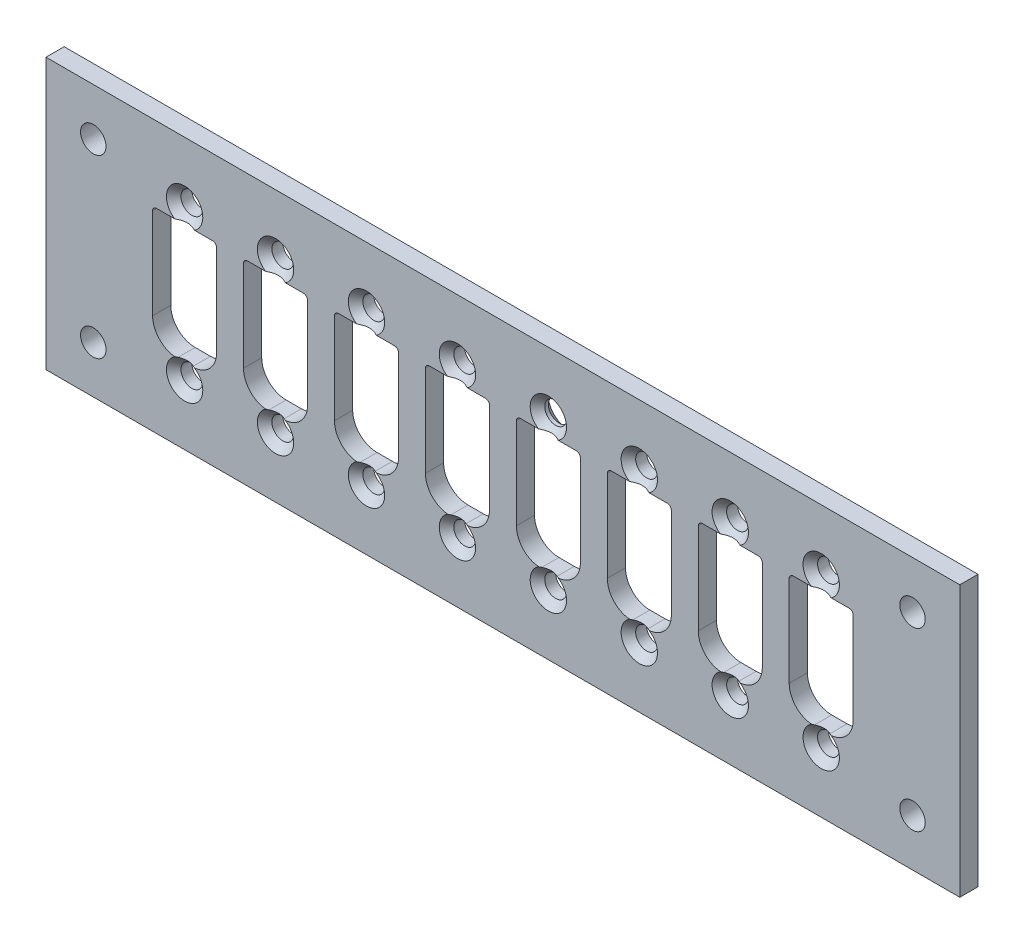
SolidWorks part; units mm, degrees
ref_plane "Front Plane" through (0, 0, 0) normal (0, 0, 1) x (1, 0, 0)
ref_plane "Top Plane" through (0, 0, 0) normal (0, 1, 0) x (1, 0, 0)
ref_plane "Right Plane" through (0, 0, 0) normal (1, 0, 0) x (0, 0, -1)
sketch "Sketch1" plane through (0, 0, 11.1151) normal (0, 0, -1) x (-1, 0, 0)
  line L0 (-135.406, 8.4004) -> (-129.506, 8.4004) construction
  line L1 (-151.506, 40.6004) -> (-25.906, 40.6004)
  line L2 (-151.506, 40.6004) -> (-151.506, 3.4004)
  line L3 (-151.506, 3.4004) -> (-25.906, 3.4004)
  line L4 (-25.906, 40.6004) -> (-25.906, 3.4004)
  line L5 (-129.506, 35.6004) -> (-135.406, 35.6004) construction
  line L6 (-40.906, 17.1504) -> (-40.906, 29.6504) construction
  line L7 (-41.106, 29.8504) -> (-48.806, 29.8504) construction
  line L8 (-49.006, 29.6504) -> (-49.006, 17.1504) construction
  line L9 (-46.006, 14.1504) -> (-43.906, 14.1504) construction
  line L10 (-53.406, 17.1504) -> (-53.406, 29.6504) construction
  line L11 (-53.606, 29.8504) -> (-61.306, 29.8504) construction
  line L12 (-61.506, 29.6504) -> (-61.506, 17.1504) construction
  line L13 (-58.506, 14.1504) -> (-56.406, 14.1504) construction
  line L14 (-65.906, 17.1504) -> (-65.906, 29.6504) construction
  line L15 (-66.106, 29.8504) -> (-73.806, 29.8504) construction
  line L16 (-74.006, 29.6504) -> (-74.006, 17.1504) construction
  line L17 (-71.006, 14.1504) -> (-68.906, 14.1504) construction
  line L18 (-78.406, 17.1504) -> (-78.406, 29.6504) construction
  line L19 (-78.606, 29.8504) -> (-86.306, 29.8504) construction
  line L20 (-86.506, 29.6504) -> (-86.506, 17.1504) construction
  line L21 (-83.506, 14.1504) -> (-81.406, 14.1504) construction
  line L22 (-90.906, 17.1504) -> (-90.906, 29.6504) construction
  line L23 (-91.106, 29.8504) -> (-98.806, 29.8504) construction
  line L24 (-99.006, 29.6504) -> (-99.006, 17.1504) construction
  line L25 (-96.006, 14.1504) -> (-93.906, 14.1504) construction
  line L26 (-103.406, 17.1504) -> (-103.406, 29.6504) construction
  line L27 (-103.606, 29.8504) -> (-111.306, 29.8504) construction
  line L28 (-111.506, 29.6504) -> (-111.506, 17.1504) construction
  line L29 (-108.506, 14.1504) -> (-106.406, 14.1504) construction
  line L30 (-115.906, 17.1504) -> (-115.906, 29.6504) construction
  line L31 (-116.106, 29.8504) -> (-123.806, 29.8504) construction
  line L32 (-124.006, 29.6504) -> (-124.006, 17.1504) construction
  line L33 (-121.006, 14.1504) -> (-118.906, 14.1504) construction
  line L34 (-128.406, 17.1504) -> (-128.406, 29.6504) construction
  line L35 (-128.606, 29.8504) -> (-136.306, 29.8504) construction
  line L36 (-136.506, 29.6504) -> (-136.506, 17.1504) construction
  line L37 (-133.506, 14.1504) -> (-131.406, 14.1504) construction
  line L38 (-40.906, 17.1504) -> (-40.906, 29.6504) construction
  line L39 (-41.106, 29.8504) -> (-48.806, 29.8504) construction
  line L40 (-49.006, 29.6504) -> (-49.006, 17.1504) construction
  line L41 (-46.006, 14.1504) -> (-43.906, 14.1504) construction
  line L42 (-53.406, 17.1504) -> (-53.406, 29.6504) construction
  line L43 (-53.606, 29.8504) -> (-61.306, 29.8504) construction
  line L44 (-61.506, 29.6504) -> (-61.506, 17.1504) construction
  line L45 (-58.506, 14.1504) -> (-56.406, 14.1504) construction
  line L46 (-65.906, 17.1504) -> (-65.906, 29.6504) construction
  line L47 (-66.106, 29.8504) -> (-73.806, 29.8504) construction
  line L48 (-74.006, 29.6504) -> (-74.006, 17.1504) construction
  line L49 (-71.006, 14.1504) -> (-68.906, 14.1504) construction
  line L50 (-78.406, 17.1504) -> (-78.406, 29.6504) construction
  line L51 (-78.606, 29.8504) -> (-86.306, 29.8504) construction
  line L52 (-86.506, 29.6504) -> (-86.506, 17.1504) construction
  line L53 (-83.506, 14.1504) -> (-81.406, 14.1504) construction
  line L54 (-90.906, 17.1504) -> (-90.906, 29.6504) construction
  line L55 (-91.106, 29.8504) -> (-98.806, 29.8504) construction
  line L56 (-99.006, 29.6504) -> (-99.006, 17.1504) construction
  line L57 (-96.006, 14.1504) -> (-93.906, 14.1504) construction
  line L58 (-103.406, 17.1504) -> (-103.406, 29.6504) construction
  line L59 (-103.606, 29.8504) -> (-111.306, 29.8504) construction
  line L60 (-111.506, 29.6504) -> (-111.506, 17.1504) construction
  line L61 (-108.506, 14.1504) -> (-106.406, 14.1504) construction
  line L62 (-115.906, 17.1504) -> (-115.906, 29.6504) construction
  line L63 (-116.106, 29.8504) -> (-123.806, 29.8504) construction
  line L64 (-124.006, 29.6504) -> (-124.006, 17.1504) construction
  line L65 (-121.006, 14.1504) -> (-118.906, 14.1504) construction
  line L66 (-128.406, 17.1504) -> (-128.406, 29.6504) construction
  line L67 (-128.606, 29.8504) -> (-136.306, 29.8504) construction
  line L68 (-136.506, 29.6504) -> (-136.506, 17.1504) construction
  line L69 (-133.506, 14.1504) -> (-131.406, 14.1504) construction
  line L70 (-61.856, 29.6504) -> (-61.856, 17.1504)
  line L71 (-58.506, 13.8004) -> (-56.406, 13.8004)
  line L72 (-53.056, 17.1504) -> (-53.056, 29.6504)
  line L73 (-53.606, 30.2004) -> (-61.306, 30.2004)
  line L74 (-49.356, 29.6504) -> (-49.356, 17.1504)
  line L75 (-46.006, 13.8004) -> (-43.906, 13.8004)
  line L76 (-40.556, 17.1504) -> (-40.556, 29.6504)
  line L77 (-41.106, 30.2004) -> (-48.806, 30.2004)
  line L78 (-74.356, 29.6504) -> (-74.356, 17.1504)
  line L79 (-71.006, 13.8004) -> (-68.906, 13.8004)
  line L80 (-65.556, 17.1504) -> (-65.556, 29.6504)
  line L81 (-66.106, 30.2004) -> (-73.806, 30.2004)
  line L82 (-86.856, 29.6504) -> (-86.856, 17.1504)
  line L83 (-83.506, 13.8004) -> (-81.406, 13.8004)
  line L84 (-78.056, 17.1504) -> (-78.056, 29.6504)
  line L85 (-78.606, 30.2004) -> (-86.306, 30.2004)
  line L86 (-99.356, 29.6504) -> (-99.356, 17.1504)
  line L87 (-96.006, 13.8004) -> (-93.906, 13.8004)
  line L88 (-90.556, 17.1504) -> (-90.556, 29.6504)
  line L89 (-91.106, 30.2004) -> (-98.806, 30.2004)
  line L90 (-111.856, 29.6504) -> (-111.856, 17.1504)
  line L91 (-108.506, 13.8004) -> (-106.406, 13.8004)
  line L92 (-103.056, 17.1504) -> (-103.056, 29.6504)
  line L93 (-103.606, 30.2004) -> (-111.306, 30.2004)
  line L94 (-124.356, 29.6504) -> (-124.356, 17.1504)
  line L95 (-121.006, 13.8004) -> (-118.906, 13.8004)
  line L96 (-115.556, 17.1504) -> (-115.556, 29.6504)
  line L97 (-116.106, 30.2004) -> (-123.806, 30.2004)
  line L98 (-136.856, 29.6504) -> (-136.856, 17.1504)
  line L99 (-133.506, 13.8004) -> (-131.406, 13.8004)
  line L100 (-128.056, 17.1504) -> (-128.056, 29.6504)
  line L101 (-128.606, 30.2004) -> (-136.306, 30.2004)
  arc A0 (-43.906, 14.1504) -> (-40.906, 17.1504) centre (-43.906, 17.1504) ccw construction
  arc A1 (-40.906, 29.6504) -> (-41.106, 29.8504) centre (-41.106, 29.6504) ccw construction
  arc A2 (-48.806, 29.8504) -> (-49.006, 29.6504) centre (-48.806, 29.6504) ccw construction
  arc A3 (-49.006, 17.1504) -> (-46.006, 14.1504) centre (-46.006, 17.1504) ccw construction
  arc A4 (-56.406, 14.1504) -> (-53.406, 17.1504) centre (-56.406, 17.1504) ccw construction
  arc A5 (-53.406, 29.6504) -> (-53.606, 29.8504) centre (-53.606, 29.6504) ccw construction
  arc A6 (-61.306, 29.8504) -> (-61.506, 29.6504) centre (-61.306, 29.6504) ccw construction
  arc A7 (-61.506, 17.1504) -> (-58.506, 14.1504) centre (-58.506, 17.1504) ccw construction
  arc A8 (-68.906, 14.1504) -> (-65.906, 17.1504) centre (-68.906, 17.1504) ccw construction
  arc A9 (-65.906, 29.6504) -> (-66.106, 29.8504) centre (-66.106, 29.6504) ccw construction
  arc A10 (-73.806, 29.8504) -> (-74.006, 29.6504) centre (-73.806, 29.6504) ccw construction
  arc A11 (-74.006, 17.1504) -> (-71.006, 14.1504) centre (-71.006, 17.1504) ccw construction
  arc A12 (-81.406, 14.1504) -> (-78.406, 17.1504) centre (-81.406, 17.1504) ccw construction
  arc A13 (-78.406, 29.6504) -> (-78.606, 29.8504) centre (-78.606, 29.6504) ccw construction
  arc A14 (-86.306, 29.8504) -> (-86.506, 29.6504) centre (-86.306, 29.6504) ccw construction
  arc A15 (-86.506, 17.1504) -> (-83.506, 14.1504) centre (-83.506, 17.1504) ccw construction
  arc A16 (-93.906, 14.1504) -> (-90.906, 17.1504) centre (-93.906, 17.1504) ccw construction
  arc A17 (-90.906, 29.6504) -> (-91.106, 29.8504) centre (-91.106, 29.6504) ccw construction
  arc A18 (-98.806, 29.8504) -> (-99.006, 29.6504) centre (-98.806, 29.6504) ccw construction
  arc A19 (-99.006, 17.1504) -> (-96.006, 14.1504) centre (-96.006, 17.1504) ccw construction
  arc A20 (-106.406, 14.1504) -> (-103.406, 17.1504) centre (-106.406, 17.1504) ccw construction
  arc A21 (-103.406, 29.6504) -> (-103.606, 29.8504) centre (-103.606, 29.6504) ccw construction
  arc A22 (-111.306, 29.8504) -> (-111.506, 29.6504) centre (-111.306, 29.6504) ccw construction
  arc A23 (-111.506, 17.1504) -> (-108.506, 14.1504) centre (-108.506, 17.1504) ccw construction
  arc A24 (-118.906, 14.1504) -> (-115.906, 17.1504) centre (-118.906, 17.1504) ccw construction
  arc A25 (-115.906, 29.6504) -> (-116.106, 29.8504) centre (-116.106, 29.6504) ccw construction
  arc A26 (-123.806, 29.8504) -> (-124.006, 29.6504) centre (-123.806, 29.6504) ccw construction
  arc A27 (-124.006, 17.1504) -> (-121.006, 14.1504) centre (-121.006, 17.1504) ccw construction
  arc A28 (-131.406, 14.1504) -> (-128.406, 17.1504) centre (-131.406, 17.1504) ccw construction
  arc A29 (-128.406, 29.6504) -> (-128.606, 29.8504) centre (-128.606, 29.6504) ccw construction
  arc A30 (-136.306, 29.8504) -> (-136.506, 29.6504) centre (-136.306, 29.6504) ccw construction
  arc A31 (-136.506, 17.1504) -> (-133.506, 14.1504) centre (-133.506, 17.1504) ccw construction
  arc A32 (-43.906, 14.1504) -> (-40.906, 17.1504) centre (-43.906, 17.1504) ccw construction
  arc A33 (-40.906, 29.6504) -> (-41.106, 29.8504) centre (-41.106, 29.6504) ccw construction
  arc A34 (-48.806, 29.8504) -> (-49.006, 29.6504) centre (-48.806, 29.6504) ccw construction
  arc A35 (-49.006, 17.1504) -> (-46.006, 14.1504) centre (-46.006, 17.1504) ccw construction
  arc A36 (-56.406, 14.1504) -> (-53.406, 17.1504) centre (-56.406, 17.1504) ccw construction
  arc A37 (-53.406, 29.6504) -> (-53.606, 29.8504) centre (-53.606, 29.6504) ccw construction
  arc A38 (-61.306, 29.8504) -> (-61.506, 29.6504) centre (-61.306, 29.6504) ccw construction
  arc A39 (-61.506, 17.1504) -> (-58.506, 14.1504) centre (-58.506, 17.1504) ccw construction
  arc A40 (-68.906, 14.1504) -> (-65.906, 17.1504) centre (-68.906, 17.1504) ccw construction
  arc A41 (-65.906, 29.6504) -> (-66.106, 29.8504) centre (-66.106, 29.6504) ccw construction
  arc A42 (-73.806, 29.8504) -> (-74.006, 29.6504) centre (-73.806, 29.6504) ccw construction
  arc A43 (-74.006, 17.1504) -> (-71.006, 14.1504) centre (-71.006, 17.1504) ccw construction
  arc A44 (-81.406, 14.1504) -> (-78.406, 17.1504) centre (-81.406, 17.1504) ccw construction
  arc A45 (-78.406, 29.6504) -> (-78.606, 29.8504) centre (-78.606, 29.6504) ccw construction
  arc A46 (-86.306, 29.8504) -> (-86.506, 29.6504) centre (-86.306, 29.6504) ccw construction
  arc A47 (-86.506, 17.1504) -> (-83.506, 14.1504) centre (-83.506, 17.1504) ccw construction
  arc A48 (-93.906, 14.1504) -> (-90.906, 17.1504) centre (-93.906, 17.1504) ccw construction
  arc A49 (-90.906, 29.6504) -> (-91.106, 29.8504) centre (-91.106, 29.6504) ccw construction
  arc A50 (-98.806, 29.8504) -> (-99.006, 29.6504) centre (-98.806, 29.6504) ccw construction
  arc A51 (-99.006, 17.1504) -> (-96.006, 14.1504) centre (-96.006, 17.1504) ccw construction
  arc A52 (-106.406, 14.1504) -> (-103.406, 17.1504) centre (-106.406, 17.1504) ccw construction
  arc A53 (-103.406, 29.6504) -> (-103.606, 29.8504) centre (-103.606, 29.6504) ccw construction
  arc A54 (-111.306, 29.8504) -> (-111.506, 29.6504) centre (-111.306, 29.6504) ccw construction
  arc A55 (-111.506, 17.1504) -> (-108.506, 14.1504) centre (-108.506, 17.1504) ccw construction
  arc A56 (-118.906, 14.1504) -> (-115.906, 17.1504) centre (-118.906, 17.1504) ccw construction
  arc A57 (-115.906, 29.6504) -> (-116.106, 29.8504) centre (-116.106, 29.6504) ccw construction
  arc A58 (-123.806, 29.8504) -> (-124.006, 29.6504) centre (-123.806, 29.6504) ccw construction
  arc A59 (-124.006, 17.1504) -> (-121.006, 14.1504) centre (-121.006, 17.1504) ccw construction
  arc A60 (-131.406, 14.1504) -> (-128.406, 17.1504) centre (-131.406, 17.1504) ccw construction
  arc A61 (-128.406, 29.6504) -> (-128.606, 29.8504) centre (-128.606, 29.6504) ccw construction
  arc A62 (-136.306, 29.8504) -> (-136.506, 29.6504) centre (-136.306, 29.6504) ccw construction
  arc A63 (-136.506, 17.1504) -> (-133.506, 14.1504) centre (-133.506, 17.1504) ccw construction
  arc A64 (-61.856, 17.1504) -> (-58.506, 13.8004) centre (-58.506, 17.1504) ccw
  arc A65 (-56.406, 13.8004) -> (-53.056, 17.1504) centre (-56.406, 17.1504) ccw
  arc A66 (-53.056, 29.6504) -> (-53.606, 30.2004) centre (-53.606, 29.6504) ccw
  arc A67 (-61.306, 30.2004) -> (-61.856, 29.6504) centre (-61.306, 29.6504) ccw
  arc A68 (-49.356, 17.1504) -> (-46.006, 13.8004) centre (-46.006, 17.1504) ccw
  arc A69 (-43.906, 13.8004) -> (-40.556, 17.1504) centre (-43.906, 17.1504) ccw
  arc A70 (-40.556, 29.6504) -> (-41.106, 30.2004) centre (-41.106, 29.6504) ccw
  arc A71 (-48.806, 30.2004) -> (-49.356, 29.6504) centre (-48.806, 29.6504) ccw
  arc A72 (-74.356, 17.1504) -> (-71.006, 13.8004) centre (-71.006, 17.1504) ccw
  arc A73 (-68.906, 13.8004) -> (-65.556, 17.1504) centre (-68.906, 17.1504) ccw
  arc A74 (-65.556, 29.6504) -> (-66.106, 30.2004) centre (-66.106, 29.6504) ccw
  arc A75 (-73.806, 30.2004) -> (-74.356, 29.6504) centre (-73.806, 29.6504) ccw
  arc A76 (-86.856, 17.1504) -> (-83.506, 13.8004) centre (-83.506, 17.1504) ccw
  arc A77 (-81.406, 13.8004) -> (-78.056, 17.1504) centre (-81.406, 17.1504) ccw
  arc A78 (-78.056, 29.6504) -> (-78.606, 30.2004) centre (-78.606, 29.6504) ccw
  arc A79 (-86.306, 30.2004) -> (-86.856, 29.6504) centre (-86.306, 29.6504) ccw
  arc A80 (-99.356, 17.1504) -> (-96.006, 13.8004) centre (-96.006, 17.1504) ccw
  arc A81 (-93.906, 13.8004) -> (-90.556, 17.1504) centre (-93.906, 17.1504) ccw
  arc A82 (-90.556, 29.6504) -> (-91.106, 30.2004) centre (-91.106, 29.6504) ccw
  arc A83 (-98.806, 30.2004) -> (-99.356, 29.6504) centre (-98.806, 29.6504) ccw
  arc A84 (-111.856, 17.1504) -> (-108.506, 13.8004) centre (-108.506, 17.1504) ccw
  arc A85 (-106.406, 13.8004) -> (-103.056, 17.1504) centre (-106.406, 17.1504) ccw
  arc A86 (-103.056, 29.6504) -> (-103.606, 30.2004) centre (-103.606, 29.6504) ccw
  arc A87 (-111.306, 30.2004) -> (-111.856, 29.6504) centre (-111.306, 29.6504) ccw
  arc A88 (-124.356, 17.1504) -> (-121.006, 13.8004) centre (-121.006, 17.1504) ccw
  arc A89 (-118.906, 13.8004) -> (-115.556, 17.1504) centre (-118.906, 17.1504) ccw
  arc A90 (-115.556, 29.6504) -> (-116.106, 30.2004) centre (-116.106, 29.6504) ccw
  arc A91 (-123.806, 30.2004) -> (-124.356, 29.6504) centre (-123.806, 29.6504) ccw
  arc A92 (-136.856, 17.1504) -> (-133.506, 13.8004) centre (-133.506, 17.1504) ccw
  arc A93 (-131.406, 13.8004) -> (-128.056, 17.1504) centre (-131.406, 17.1504) ccw
  arc A94 (-128.056, 29.6504) -> (-128.606, 30.2004) centre (-128.606, 29.6504) ccw
  arc A95 (-136.306, 30.2004) -> (-136.856, 29.6504) centre (-136.306, 29.6504) ccw
  circle A96 centre (-57.456, 11.7004) radius 1.5 construction
  circle A97 centre (-44.956, 11.7004) radius 1.5 construction
  circle A98 centre (-44.956, 32.3004) radius 1.5 construction
  circle A99 centre (-57.456, 11.7004) radius 1.5
  circle A100 centre (-44.956, 11.7004) radius 1.5
  circle A101 centre (-44.956, 32.3004) radius 1.5
  circle A102 centre (-132.456, 32.3004) radius 1.5 construction
  circle A103 centre (-132.456, 11.7004) radius 1.5 construction
  circle A104 centre (-119.956, 11.7004) radius 1.5 construction
  circle A105 centre (-119.956, 32.3004) radius 1.5 construction
  circle A106 centre (-107.456, 32.3004) radius 1.5 construction
  circle A107 centre (-107.456, 11.7004) radius 1.5 construction
  circle A108 centre (-94.956, 11.7004) radius 1.5 construction
  circle A109 centre (-94.956, 32.3004) radius 1.5 construction
  circle A110 centre (-82.456, 32.3004) radius 1.5 construction
  circle A111 centre (-82.456, 11.7004) radius 1.5 construction
  circle A112 centre (-69.956, 11.7004) radius 1.5 construction
  circle A113 centre (-69.956, 32.3004) radius 1.5 construction
  circle A114 centre (-57.456, 32.3004) radius 1.5 construction
  circle A115 centre (-132.456, 32.3004) radius 1.5
  circle A116 centre (-132.456, 11.7004) radius 1.5
  circle A117 centre (-119.956, 11.7004) radius 1.5
  circle A118 centre (-119.956, 32.3004) radius 1.5
  circle A119 centre (-107.456, 32.3004) radius 1.5
  circle A120 centre (-107.456, 11.7004) radius 1.5
  circle A121 centre (-94.956, 11.7004) radius 1.5
  circle A122 centre (-94.956, 32.3004) radius 1.5
  circle A123 centre (-82.456, 32.3004) radius 1.5
  circle A124 centre (-82.456, 11.7004) radius 1.5
  circle A125 centre (-69.956, 11.7004) radius 1.5
  circle A126 centre (-69.956, 32.3004) radius 1.5
  circle A127 centre (-57.456, 32.3004) radius 1.5
  dimension "D1" = 5
  dimension "D2" = 5
  dimension "D3" = 15
  dimension "D4" = 15
  dimension "D5" = 0.35
extrude "Boss-Extrude1" add sketch "Sketch1" against normal blind 2.5
chamfer "Chamfer2" distance 1 angle 45 17 edges at (93.456, 32.3004, 11.1151) (93.456, 32.3004, 13.6151) (130.956, 32.3004, 13.6151) (130.956, 11.7004, 13.6151) (118.456, 11.7004, 13.6151) (118.456, 32.3004, 13.6151) (105.956, 32.3004, 13.6151) (105.956, 11.7004, 13.6151) (93.456, 11.7004, 13.6151) (80.956, 32.3004, 13.6151) (80.956, 11.7004, 13.6151) (68.456, 11.7004, 13.6151) (68.456, 32.3004, 13.6151) (55.956, 32.3004, 13.6151) (55.956, 11.7004, 13.6151) (43.456, 11.7004, 13.6151) (43.456, 32.3004, 13.6151)
sketch "Sketch2" plane through (0, 0, 13.6151) normal (0, 0, 1) x (1, 0, 0)
  circle A0 centre (145.006, 9.9004) radius 2.5 construction
  circle A1 centre (145.006, 34.1004) radius 2.5 construction
  circle A2 centre (32.406, 9.9004) radius 2.5 construction
  circle A3 centre (32.406, 34.1004) radius 2.5 construction
  circle A4 centre (145.006, 9.9004) radius 2.5
  circle A5 centre (145.006, 34.1004) radius 2.5
  circle A6 centre (32.406, 9.9004) radius 2.5
  circle A7 centre (32.406, 34.1004) radius 2.5
  circle A8 centre (145.006, 34.1004) radius 1.75
  circle A9 centre (145.006, 9.9004) radius 1.75
  circle A10 centre (32.406, 9.9004) radius 1.75
  circle A11 centre (32.406, 34.1004) radius 1.75
  dimension "D1" = 3.5
  dimension "D2" = 3.5
  dimension "D3" = 3.5
  dimension "D4" = 3.5
extrude "Cut-Extrude1" cut sketch "Sketch2" against normal through all contours A8 | A9 | A10 | A11 region at (145.006, 34.1004, 13.6151) region at (145.006, 9.9004, 13.6151) region at (32.406, 9.9004, 13.6151) region at (32.406, 34.1004, 13.6151)
